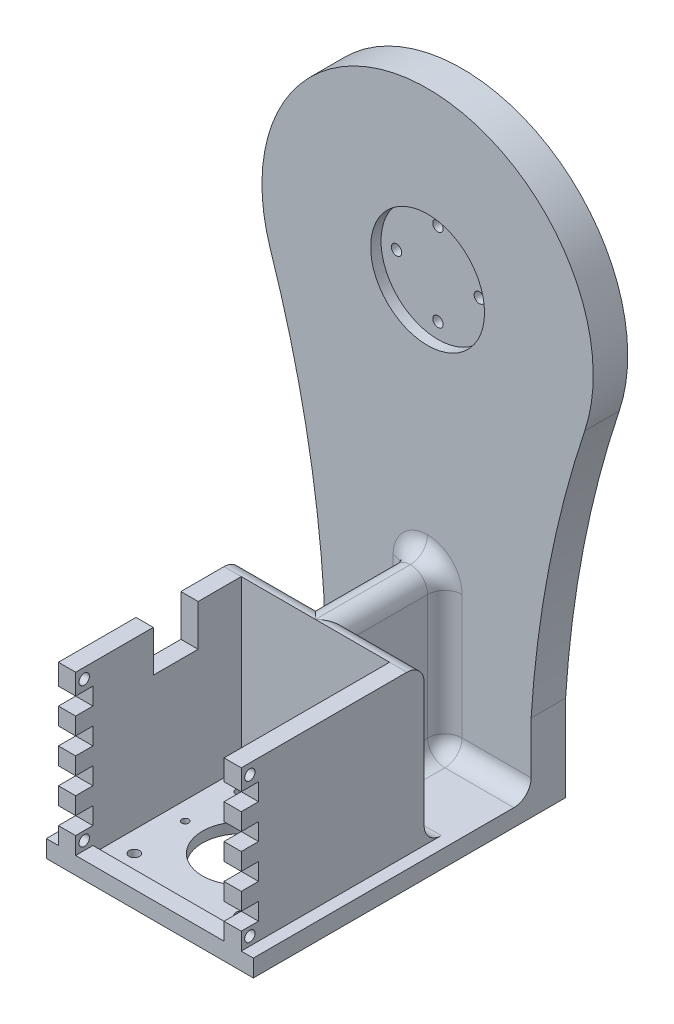
SolidWorks part; units mm, degrees
note: '?' marks a value the reader was unsure of.
ref_plane "Alzado" through (0, 0, 0) normal (0, 0, 1) x (1, 0, 0)
ref_plane "Planta" through (0, 0, 0) normal (0, 1, 0) x (1, 0, 0)
ref_plane "Vista lateral" through (0, 0, 0) normal (1, 0, 0) x (0, 0, -1)
sketch "Croquis1" plane through (0, 0, 0) normal (0, 0, 1) x (1, 0, 0)
  line L0 (-30, -115) -> (-190.8494, -115)
  line L1 (-30, -115) -> (30, -115)
  line L2 (-30, -115) -> (-30, -95)
  line L3 (-30, -95) -> (30, -95)
  line L4 (30, -115) -> (30, -95)
  line L5 (0, 0) -> (0, -95)
  circle A1 centre (0, 0) radius 48
  arc A2 (-30, -95) -> (-45.5442, -15.1567) centre (-345.5616, -115) ccw
  arc A3 (30, -95) -> (45.5442, -15.1567) centre (345.5616, -115) cw
  dimension "D2" = 96
  dimension "D3" = 60
  dimension "D4" = 20
  dimension "D6" = 95
extrude "Saliente-Extruir1" add sketch "Croquis1" along normal blind 10
sketch "Croquis4" plane through (0, 0, 10) normal (0, 0, 1) x (-1, 0, 0)
  line L0 (0, 0) -> (0, 12) construction
  circle A9 centre (0, 0) radius 12
  circle A10 centre (0, 12) radius 1.5
  circle A11 centre (12, 0) radius 1.5
  circle A12 centre (0, -12) radius 1.5
  circle A13 centre (-12, 0) radius 1.5
  dimension "D1" = 24
  dimension "D2" = 3
  dimension "D3" = 4
  dimension "D4" = 12
  dimension "D5" = 12
sketch "Croquis5" plane through (0, 0, 10) normal (0, 0, 1) x (1, 0, 0)
  circle A0 centre (0, 0) radius 16.5
  dimension "D1" = 33
extrude "Cortar-Extruir4" cut sketch "Croquis5" against normal blind 3
extrude "Cortar-Extruir8" cut sketch "Croquis4" against normal through all contours A9 A10 | A9 A13 | L0 A10 A9 | A10 L0 A9 | A9 A12 | A9 A12 | A9 A11 | A9 A11
sketch "Croquis6" plane through (0, -115, 0) normal (0, -1, 0) x (1, 0, 0)
  line L0 (-30, 10) -> (-30, 0) construction
  line L1 (-30, 0) -> (30, 0)
  line L2 (-30, 0) -> (-30, 90.5)
  line L3 (-30, 90.5) -> (30, 90.5)
  line L4 (30, 0) -> (30, 90.5)
  line L5 (-30, 0) -> (30, 0) construction
  dimension "D1" = 90.5
extrude "Saliente-Extruir2" add sketch "Croquis6" along normal blind 5
ref_plane "Plano1" through (0, 0, 64) normal (0, 0, 1) x (1, 0, 0)
ref_axis "center_axis" through (0, -51.344, 64) along (0, 1, 0)?
sketch "Croquis7" plane through (0, -120, 0) normal (0, -1, 0) x (1, 0, 0)
  circle A0 centre (0, 64) radius 11.25
  circle A1 centre (-15.5, 79.5) radius 1.5
  circle A2 centre (15.5, 79.5) radius 1.5
  circle A3 centre (15.5, 48.5) radius 1.5
  circle A4 centre (-15.5, 48.5) radius 1.5
  dimension "D1" = 22.5
  dimension "D6" = 3
  dimension "D3" = 15.5
  dimension "D7" = 31
  dimension "D8" = 31
  dimension "D9" = 15.5
  dimension "D2" = 15.5
  dimension "D4" = 2
  dimension "D5" = 2
extrude "Cortar-Extruir9" cut sketch "Croquis7" against normal blind 10
sketch "Croquis8" plane through (0, -115, 0) normal (0, 1, 0) x (1, 0, 0)
  line L1 (-21.5, -42.5) -> (21.5, -42.5)
  line L2 (-21.5, -42.5) -> (-21.5, -90.5)
  line L4 (21.5, -42.5) -> (21.5, -90.5)
  line L6 (-26.5, -90.5) -> (-26.5, -37.5)
  line L7 (-26.5, -37.5) -> (26.5, -37.5)
  line L8 (26.5, -90.5) -> (26.5, -37.5)
  line L9 (30, -90.5) -> (-30, -90.5) construction
  line L10 (-26.5, -90.5) -> (-21.5, -90.5)
  line L11 (21.5, -90.5) -> (26.5, -90.5)
  dimension "D3" = 21.5
  dimension "D4" = 21.5
  dimension "D5" = 5
  dimension "D6" = 5
  dimension "D7" = 5
  dimension "D8" = 21.5
extrude "Saliente-Extruir3" add sketch "Croquis8" along normal blind 46
sketch "Croquis10" plane through (0, 0, 90.5) normal (0, 0, 1) x (1, 0, 0)
  line L0 (26.5, -69) -> (26.5, -115) construction
  line L1 (26.5, -110) -> (21.5, -110)
  line L2 (26.5, -110) -> (26.5, -105)
  line L3 (26.5, -105) -> (21.5, -105)
  line L4 (21.5, -110) -> (21.5, -105)
  line L5 (30, -115) -> (26.5, -115) construction
  line L6 (-26.5, -69) -> (-26.5, -115) construction
  line L7 (-26.5, -110) -> (-21.5, -110)
  line L8 (-26.5, -110) -> (-26.5, -105)
  line L9 (-26.5, -105) -> (-21.5, -105)
  line L10 (-21.5, -110) -> (-21.5, -105)
  line L11 (-26.5, -100) -> (-26.5, -95)
  line L12 (-26.5, -115) -> (-30, -115) construction
  line L22 (21.5, -69) -> (21.5, -115) construction
  line L24 (-21.5, -69) -> (-21.5, -115) construction
  line L25 (-26.5, -100) -> (-21.5, -100)
  line L26 (-21.5, -100) -> (-21.5, -95)
  line L27 (-26.5, -95) -> (-21.5, -95)
  line L28 (26.5, -100) -> (26.5, -95)
  line L29 (26.5, -100) -> (21.5, -100)
  line L30 (21.5, -100) -> (21.5, -95)
  line L31 (26.5, -95) -> (21.5, -95)
  line L32 (-26.5, -90) -> (-26.5, -85)
  line L33 (-26.5, -90) -> (-21.5, -90)
  line L34 (-21.5, -90) -> (-21.5, -85)
  line L35 (-26.5, -85) -> (-21.5, -85)
  line L36 (26.5, -90) -> (26.5, -85)
  line L37 (26.5, -90) -> (21.5, -90)
  line L38 (21.5, -90) -> (21.5, -85)
  line L39 (26.5, -85) -> (21.5, -85)
  line L40 (-26.5, -80) -> (-26.5, -75)
  line L41 (-26.5, -80) -> (-21.5, -80)
  line L42 (-21.5, -80) -> (-21.5, -75)
  line L43 (-26.5, -75) -> (-21.5, -75)
  line L44 (26.5, -80) -> (26.5, -75)
  line L45 (26.5, -80) -> (21.5, -80)
  line L46 (21.5, -80) -> (21.5, -75)
  line L47 (26.5, -75) -> (21.5, -75)
  line L56 (-26.5, -65) -> (-21.5, -65) [skipped]
  line L57 (-26.5, -70) -> (-21.5, -70) [skipped]
  line L58 (26.5, -65) -> (21.5, -65) [skipped]
  line L59 (26.5, -70) -> (21.5, -70) [skipped]
  line L60 (21.5, -70) -> (21.5, -65) [skipped]
  line L61 (26.5, -70) -> (26.5, -65) [skipped]
  line L62 (-21.5, -70) -> (-21.5, -65) [skipped]
  line L63 (-26.5, -70) -> (-26.5, -65) [skipped]
  dimension "D1" = 5
  dimension "D2" = 5
  dimension "D3" = 5
  dimension "D4" = 5
  dimension "D8" = 5
extrude "Cortar-Extruir11" cut sketch "Croquis10" against normal blind 5
sketch "Croquis11" plane through (-26.5, 0, 0) normal (-1, 0, 0) x (0, 0, 1)
  line L0 (90.5, -115) -> (10, -115) construction
  line L1 (90.5, -110) -> (90.5, -115) construction
  line L3 (90.5, -69) -> (90.5, -75) construction
  line L4 (85.5, -75) -> (90.5, -75) construction
  circle A0 centre (88, -112.5) radius 1.5
  circle A1 centre (88, -72) radius 1.5
  dimension "D1" = 3
  dimension "D4" = 3
  dimension "D2" = 2.5
  dimension "D3" = 2.5
  dimension "D5" = 3
  dimension "D6" = 2.5
extrude "Cortar-Extruir12" cut sketch "Croquis11" against normal through all
sketch "Croquis13" plane through (0, -115, 0) normal (0, 1, 0) x (1, 0, 0)
  line L1 (-21.5, -42.5) -> (21.5, -42.5)
  line L2 (-21.5, -42.5) -> (-21.5, -85.5)
  line L3 (-21.5, -85.5) -> (21.5, -85.5)
  line L4 (21.5, -42.5) -> (21.5, -85.5)
  dimension "D1" = 43
extrude "Cortar-Extruir13" cut sketch "Croquis13" against normal blind 2
sketch "Croquis16" plane through (0, -120, 0) normal (0, -1, 0) x (1, 0, 0)
  line L1 (-23, 64) -> (23, 64)
  line L2 (30, 90.5) -> (-30, 90.5) construction
  circle A4 centre (-16.25, 64) radius 1
  circle A5 centre (16.25, 64) radius 1
  circle A6 centre (0, 64) radius 11.25 construction
  circle A7 centre (-23, 64) radius 1
  circle A8 centre (23, 64) radius 1
  dimension "D5" = 2
  dimension "D6" = 2
  dimension "D7" = 2
  dimension "D8" = 2
  dimension "D3" = 16.25
  dimension "D4" = 16.25
  dimension "D9" = 6.75
  dimension "D10" = 6.75
  dimension "D11" = 26.5
extrude "Cortar-Extruir14" cut sketch "Croquis16" against normal blind 10
sketch "Croquis17" plane through (0, 0, 0) normal (1, 0, 0) x (0, 0, -1)
  line L0 (-37.5, -69) -> (-10, -69)
  line L1 (-10, -15.1567) -> (-10, -95) construction
  dimension "D1" = 46
rib "Nervio1" sketch "Croquis17" sketch "Croquis17" thickness 10 extrusion direction parallel to sketch draft on no parameters "D1"=10
fillet "Redondeo2" radius 5 12 edges at (-5, -92, 10) (5, -92, 10) (17.5, -115, 10) (-17.5, -115, 10) (-15.75, -115, 37.5) (-5, -115, 23.75) (15.75, -115, 37.5) (5, -115, 23.75) (-15.75, -69, 37.5) (-5, -69, 23.75) (5, -69, 23.75) (15.75, -69, 37.5)
sketch "Croquis18" plane through (-26.5, 0, 0) normal (-1, 0, 0) x (0, 0, 1)
  line L1 (68, -69) -> (55, -69)
  line L2 (68, -69) -> (68, -81)
  line L3 (68, -81) -> (55, -81)
  line L4 (55, -69) -> (55, -81)
  line L7 (85.5, -75) -> (85.5, -80) construction
  line L8 (37.5, -74) -> (37.5, -110) construction
  line L10 (42.5, -69) -> (90.5, -69) construction
  point P12 (68, -75)
  dimension "D1" = 17.5
  dimension "D2" = 17.5
  dimension "D3" = 12
extrude "Cortar-Extruir15" cut sketch "Croquis18" against normal blind 10
